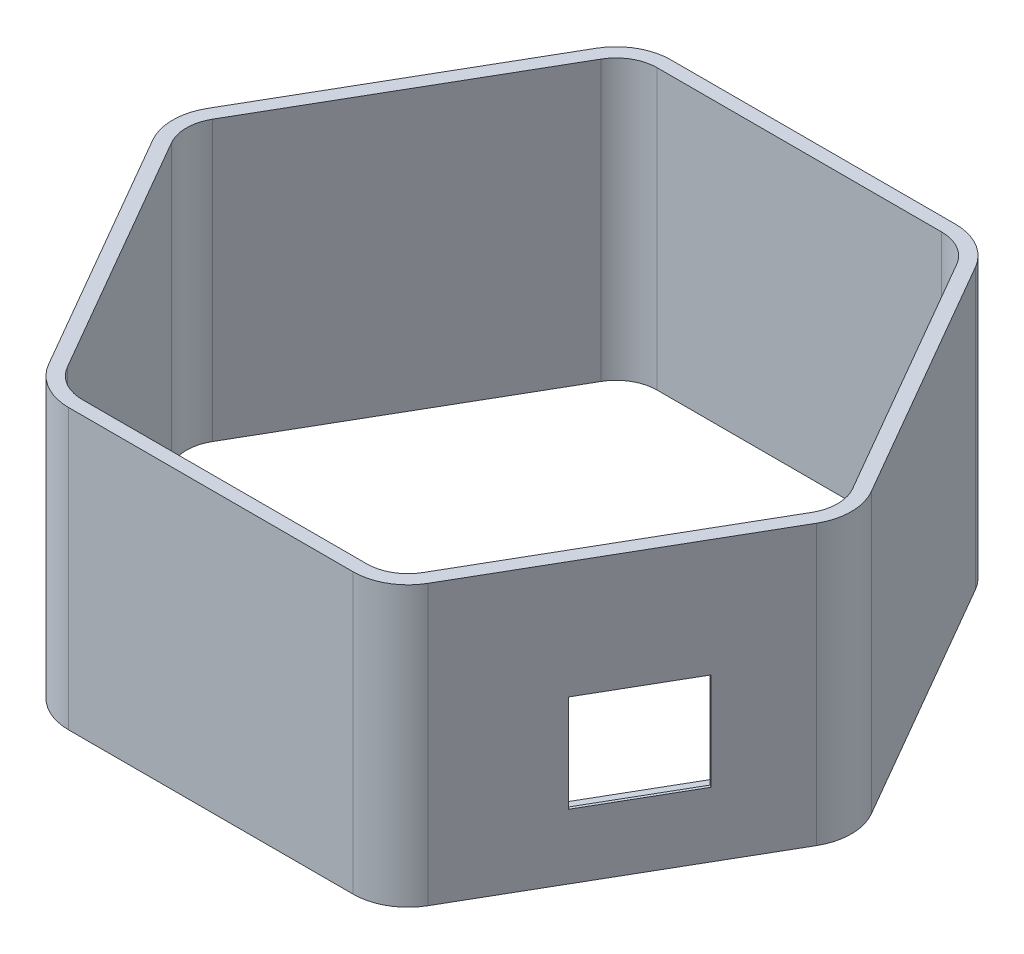
SolidWorks part; units mm, degrees
ref_plane "Front" through (0, 0, 0) normal (0, 0, 1) x (1, 0, 0)
ref_plane "Top" through (0, 0, 0) normal (0, 1, 0) x (1, 0, 0)
ref_plane "Right" through (0, 0, 0) normal (1, 0, 0) x (0, 0, -1)
sketch "Croquis1" plane through (0, 0, 0) normal (0, 1, 0) x (1, 0, 0)
  line L1 (-121.2436, -10) -> (-69.282, -100)
  line L2 (-51.9615, -110) -> (51.9615, -110)
  line L3 (69.282, -100) -> (121.2436, -10)
  line L4 (121.2436, 10) -> (69.282, 100)
  line L5 (51.9615, 110) -> (-51.9615, 110)
  line L6 (-69.282, 100) -> (-121.2436, 10)
  circle A0 centre (0, 0) radius 110 construction
  arc A1 (-69.282, 100) -> (-51.9615, 110) centre (-51.9615, 90) cw
  arc A2 (69.282, 100) -> (51.9615, 110) centre (51.9615, 90) ccw
  arc A3 (121.2436, -10) -> (121.2436, 10) centre (103.923, 0) ccw
  arc A4 (51.9615, -110) -> (69.282, -100) centre (51.9615, -90) ccw
  arc A5 (-69.282, -100) -> (-51.9615, -110) centre (-51.9615, -90) ccw
  arc A6 (-121.2436, -10) -> (-121.2436, 10) centre (-103.923, 0) cw
  dimension "D1" = 220
  dimension "D2" = 20
extrude "Saliente-Extruir1" add sketch "Croquis1" along normal blind 2
sketch "Croquis2" plane through (0, 2, 0) normal (0, 1, 0) x (1, 0, 0)
  line L6 (-64.9519, 97.5) -> (-116.9134, 7.5)
  line L7 (-116.9134, -7.5) -> (-64.9519, -97.5)
  line L8 (-51.9615, -105) -> (51.9615, -105)
  line L9 (64.9519, -97.5) -> (116.9134, -7.5)
  line L10 (116.9134, 7.5) -> (64.9519, 97.5)
  line L11 (51.9615, 105) -> (-51.9615, 105)
  line L12 (-69.282, 100) -> (-121.2436, 10)
  line L13 (-121.2436, -10) -> (-69.282, -100)
  line L14 (-51.9615, -110) -> (51.9615, -110)
  line L15 (69.282, -100) -> (121.2436, -10)
  line L16 (121.2436, 10) -> (69.282, 100)
  line L17 (51.9615, 110) -> (-51.9615, 110)
  line L18 (-69.282, 100) -> (-121.2436, 10)
  line L19 (-121.2436, -10) -> (-69.282, -100)
  line L20 (-51.9615, -110) -> (51.9615, -110)
  line L21 (69.282, -100) -> (121.2436, -10)
  line L22 (121.2436, 10) -> (69.282, 100)
  line L23 (51.9615, 110) -> (-51.9615, 110)
  arc A6 (-116.9134, 7.5) -> (-116.9134, -7.5) centre (-103.923, 0) ccw
  arc A7 (-64.9519, -97.5) -> (-51.9615, -105) centre (-51.9615, -90) ccw
  arc A8 (51.9615, -105) -> (64.9519, -97.5) centre (51.9615, -90) ccw
  arc A9 (116.9134, -7.5) -> (116.9134, 7.5) centre (103.923, 0) ccw
  arc A10 (64.9519, 97.5) -> (51.9615, 105) centre (51.9615, 90) ccw
  arc A11 (-51.9615, 105) -> (-64.9519, 97.5) centre (-51.9615, 90) ccw
  arc A12 (-51.9615, 110) -> (-69.282, 100) centre (-51.9615, 90) ccw
  arc A13 (-121.2436, 10) -> (-121.2436, -10) centre (-103.923, 0) ccw
  arc A14 (-69.282, -100) -> (-51.9615, -110) centre (-51.9615, -90) ccw
  arc A15 (51.9615, -110) -> (69.282, -100) centre (51.9615, -90) ccw
  arc A16 (121.2436, -10) -> (121.2436, 10) centre (103.923, 0) ccw
  arc A17 (69.282, 100) -> (51.9615, 110) centre (51.9615, 90) ccw
  arc A18 (-51.9615, 110) -> (-69.282, 100) centre (-51.9615, 90) ccw
  arc A19 (-121.2436, 10) -> (-121.2436, -10) centre (-103.923, 0) ccw
  arc A20 (-69.282, -100) -> (-51.9615, -110) centre (-51.9615, -90) ccw
  arc A21 (51.9615, -110) -> (69.282, -100) centre (51.9615, -90) ccw
  arc A22 (121.2436, -10) -> (121.2436, 10) centre (103.923, 0) ccw
  arc A23 (69.282, 100) -> (51.9615, 110) centre (51.9615, 90) ccw
  dimension "D1" = 0
  dimension "D2" = 5
extrude "Saliente-Extruir2" add sketch "Croquis2" along normal blind 100
sketch "Croquis3" plane through (90.9327, 0, 52.5) normal (-0.866, 0, -0.5) x (-0.5, 0, 0.866)
  line L0 (51.9615, 0) -> (-51.9615, 0) construction
  line L1 (22.0238, 60.6352) -> (22.0238, 22.4352)
  line L2 (22.0238, 60.6352) -> (-36.6762, 60.6352)
  line L3 (-36.6762, 60.6352) -> (-36.6762, 22.4352)
  line L4 (22.0238, 22.4352) -> (-36.6762, 22.4352)
  line L5 (-23.7762, 59.4352) -> (15.0238, 59.4352)
  line L6 (-23.7762, 59.4352) -> (-23.7762, 23.6352)
  line L7 (-23.7762, 23.6352) -> (15.0238, 23.6352)
  line L8 (15.0238, 59.4352) -> (15.0238, 23.6352)
  line L9 (51.9615, 102) -> (51.9615, 0) construction
  circle A0 centre (19.0238, 57.6352) radius 1.5
  circle A1 centre (19.0238, 25.4352) radius 1.5
  circle A2 centre (-33.6762, 25.4352) radius 1.5
  circle A3 centre (-33.6762, 57.6352) radius 1.5
  dimension "D1" = 3
  dimension "D2" = 3
  dimension "D3" = 58.7
  dimension "D4" = 3
  dimension "D5" = 3
  dimension "D6" = 3
  dimension "D7" = 3
  dimension "D8" = 3
  dimension "D9" = 3
  dimension "D10" = 3
  dimension "D11" = 38.2
  dimension "D12" = 35.8
  dimension "D13" = 38.8
  dimension "D14" = 1.2
  dimension "D15" = 7
  dimension "D16" = 23.6352
  dimension "D17" = 36.9377
extrude "Cortar-Extruir1" cut sketch "Croquis3" against normal blind 1
sketch "Croquis4" plane through (90.9327, 0, 52.5) normal (-0.866, 0, -0.5) x (-0.5, 0, 0.866)
  line L4 (15.0238, 59.4352) -> (-23.7762, 59.4352)
  line L5 (-23.7762, 59.4352) -> (-23.7762, 23.6352)
  line L6 (-23.7762, 23.6352) -> (15.0238, 23.6352)
  line L7 (15.0238, 23.6352) -> (15.0238, 59.4352)
  line L8 (14.4057, 59.1644) -> (-23.7762, 59.1644)
  line L9 (-23.7762, 59.1644) -> (-23.7762, 23.6352)
  line L10 (-23.7762, 23.6352) -> (14.4057, 23.6352)
  line L11 (14.4057, 23.6352) -> (14.4057, 59.1644)
  dimension "D1" = 0
extrude "Cortar-Extruir2" cut sketch "Croquis4" against normal blind 12
sketch "Croquis5" plane through (91.7987, 0, 53) normal (-0.866, 0, -0.5) x (-0.5, 0, 0.866)
  line L4 (22.0238, 60.6352) -> (-36.6762, 60.6352)
  line L5 (-36.6762, 60.6352) -> (-36.6762, 22.4352)
  line L6 (-36.6762, 22.4352) -> (22.0238, 22.4352)
  line L7 (22.0238, 22.4352) -> (22.0238, 60.6352)
  line L8 (22.0238, 60.6352) -> (-36.6762, 60.6352)
  line L9 (-36.6762, 60.6352) -> (-36.6762, 22.4352)
  line L10 (-36.6762, 22.4352) -> (22.0238, 22.4352)
  line L11 (22.0238, 22.4352) -> (22.0238, 60.6352)
  circle A0 centre (19.0238, 25.4352) radius 1.5 construction
  circle A1 centre (19.0238, 57.6352) radius 1.5 construction
  circle A2 centre (-33.6762, 57.6352) radius 1.5 construction
  circle A3 centre (-33.6762, 25.4352) radius 1.5 construction
  circle A4 centre (19.0238, 25.4352) radius 1.5
  circle A5 centre (19.0238, 57.6352) radius 1.5
  circle A6 centre (-33.6762, 57.6352) radius 1.5
  circle A7 centre (-33.6762, 25.4352) radius 1.5
  dimension "D1" = 0
extrude "Cortar-Extruir3" cut sketch "Croquis5" against normal blind 3
sketch "Croquis6" plane through (94.3968, 0, 54.5) normal (-0.866, 0, -0.5) x (-0.5, 0, 0.866)
  line L1 (-36.6762, 60.6352) -> (-31.6762, 60.6352)
  line L2 (-36.6762, 60.6352) -> (-36.6762, 55.6352)
  line L3 (-36.6762, 55.6352) -> (-32.6762, 55.6352)
  line L4 (-31.6762, 60.6352) -> (-31.6762, 56.6352)
  line L5 (-36.6762, 22.4352) -> (-31.6762, 22.4352)
  line L6 (-36.6762, 22.4352) -> (-36.6762, 27.4352)
  line L7 (-36.6762, 27.4352) -> (-32.6762, 27.4352)
  line L8 (-31.6762, 22.4352) -> (-31.6762, 26.4352)
  line L9 (22.0238, 22.4352) -> (17.0238, 22.4352)
  line L10 (22.0238, 22.4352) -> (22.0238, 27.4352)
  line L11 (22.0238, 27.4352) -> (18.0238, 27.4352)
  line L12 (17.0238, 22.4352) -> (17.0238, 26.4352)
  line L13 (22.0238, 60.6352) -> (17.0238, 60.6352)
  line L14 (22.0238, 60.6352) -> (22.0238, 55.6352)
  line L15 (22.0238, 55.6352) -> (18.0238, 55.6352)
  line L16 (17.0238, 60.6352) -> (17.0238, 56.6352)
  line L17 (-36.6762, 60.6352) -> (-36.6762, 22.4352) construction
  circle A2 centre (-33.6762, 25.4352) radius 1
  circle A4 centre (19.0238, 57.6352) radius 1
  circle A5 centre (19.0238, 25.4352) radius 1
  arc A6 (-32.6762, 55.6352) -> (-31.6762, 56.6352) centre (-32.6762, 56.6352) ccw
  arc A7 (-31.6762, 26.4352) -> (-32.6762, 27.4352) centre (-32.6762, 26.4352) ccw
  arc A8 (17.0238, 26.4352) -> (18.0238, 27.4352) centre (18.0238, 26.4352) cw
  arc A9 (18.0238, 55.6352) -> (17.0238, 56.6352) centre (18.0238, 56.6352) cw
  point P39 (-31.6762, 55.6352)
  dimension "D1" = 5
  dimension "D9" = 1
  dimension "D2" = 5
  dimension "D3" = 5
  dimension "D4" = 5
  dimension "D5" = 5
  dimension "D6" = 5
  dimension "D7" = 5
  dimension "D8" = 5
sketch "Croquis8" plane through (90.9327, 0, 52.5) normal (-0.866, 0, -0.5) x (-0.5, 0, 0.866)
  circle A0 centre (-33.6762, 57.6352) radius 1
  circle A1 centre (-33.6762, 25.4352) radius 1
  circle A2 centre (19.0238, 25.4352) radius 1
  circle A3 centre (19.0238, 57.6352) radius 1
extrude "Cortar-Extruir5" cut sketch "Croquis8" against normal up to surface (4 mm away) up to face at (98.0599, 41.5352, 48.1553)
sketch "Croquis11" plane through (0, 2, 0) normal (0, 1, 0) x (1, 0, 0)
  line L12 (51.9615, 105) -> (-51.9615, 105)
  line L13 (-64.9519, 97.5) -> (-116.9134, 7.5)
  line L14 (-116.9134, -7.5) -> (-64.9519, -97.5)
  line L15 (-51.9615, -105) -> (51.9615, -105)
  line L16 (64.9519, -97.5) -> (116.9134, -7.5)
  line L17 (116.9134, 7.5) -> (64.9519, 97.5)
  line L18 (51.9615, 105) -> (-51.9615, 105)
  line L19 (-64.9519, 97.5) -> (-116.9134, 7.5)
  line L20 (-116.9134, -7.5) -> (-64.9519, -97.5)
  line L21 (-51.9615, -105) -> (51.9615, -105)
  line L22 (64.9519, -97.5) -> (116.9134, -7.5)
  line L23 (116.9134, 7.5) -> (64.9519, 97.5)
  arc A12 (-51.9615, 105) -> (-64.9519, 97.5) centre (-51.9615, 90) ccw
  arc A13 (-116.9134, 7.5) -> (-116.9134, -7.5) centre (-103.923, 0) ccw
  arc A14 (-64.9519, -97.5) -> (-51.9615, -105) centre (-51.9615, -90) ccw
  arc A15 (51.9615, -105) -> (64.9519, -97.5) centre (51.9615, -90) ccw
  arc A16 (116.9134, -7.5) -> (116.9134, 7.5) centre (103.923, 0) ccw
  arc A17 (64.9519, 97.5) -> (51.9615, 105) centre (51.9615, 90) ccw
  arc A18 (-51.9615, 105) -> (-64.9519, 97.5) centre (-51.9615, 90) ccw
  arc A19 (-116.9134, 7.5) -> (-116.9134, -7.5) centre (-103.923, 0) ccw
  arc A20 (-64.9519, -97.5) -> (-51.9615, -105) centre (-51.9615, -90) ccw
  arc A21 (51.9615, -105) -> (64.9519, -97.5) centre (51.9615, -90) ccw
  arc A22 (116.9134, -7.5) -> (116.9134, 7.5) centre (103.923, 0) ccw
  arc A23 (64.9519, 97.5) -> (51.9615, 105) centre (51.9615, 90) ccw
  dimension "D1" = 0
extrude "Cortar-Extruir7" cut sketch "Croquis11" against normal blind 10
extrude "Saliente-Extruir3" add sketch "Croquis6" along normal blind 2.5
